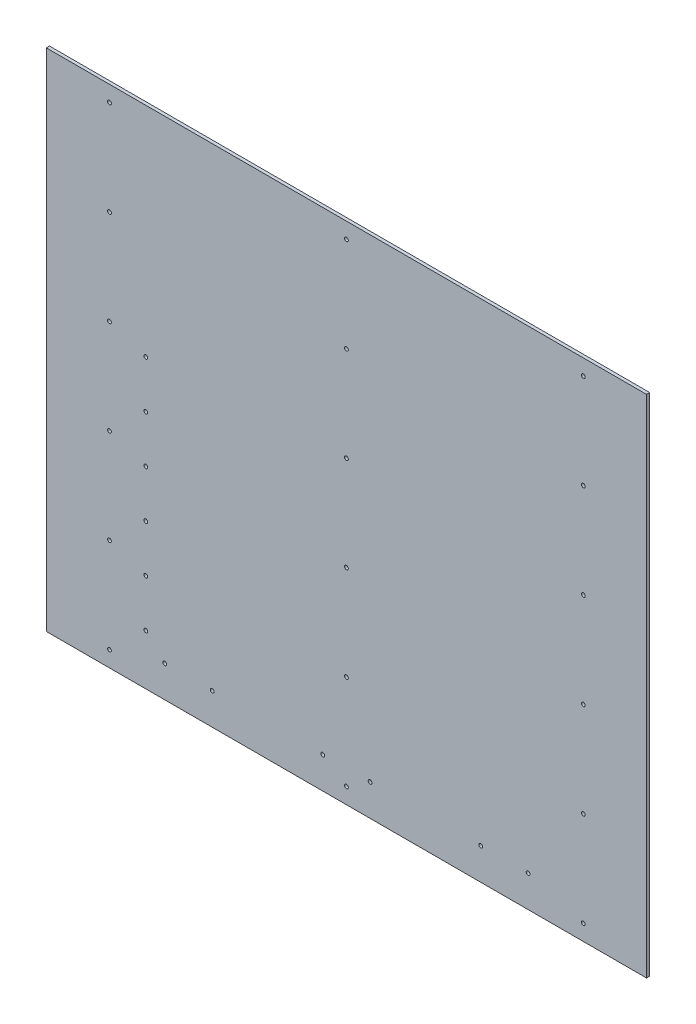
SolidWorks part; units mm, degrees
ref_plane "Płaszczyzna przednia" through (0, 0, 0) normal (0, 0, 1) x (1, 0, 0)
ref_plane "Płaszczyzna górna" through (0, 0, 0) normal (0, 1, 0) x (1, 0, 0)
ref_plane "Płaszczyzna prawa" through (0, 0, 0) normal (1, 0, 0) x (0, 0, -1)
sketch "Szkic1" plane through (0, 0, 0) normal (0, 0, 1) x (1, 0, 0)
  line L1 (-950, -800) -> (950, -800)
  line L2 (-950, -800) -> (-950, 800)
  line L3 (-950, 800) -> (950, 800)
  line L4 (950, -800) -> (950, 800)
  line L5 (-950, -800) -> (950, 800) construction
  line L6 (-950, 800) -> (950, -800) construction
  point P0 (0, 0)
  dimension "D1" = 1900
  dimension "D2" = 1600
extrude "Dodanie-wyciągnięcie1" add sketch "Szkic1" along normal blind 10
hole_wizard "Otwór pod śrubę M101" positions "Szkic2" profile "Szkic3" hole size "M10" standard "Ansi Metric" end condition through all
sketch "Szkic2" plane through (0, 0, 10) normal (0, 0, 1) x (1, 0, 0)
  line L0 (-950, 800) -> (-950, -800) construction
  line L2 (-950, -800) -> (950, -800) construction
  point P0 (-750, -750)
  dimension "D1" = 200
  dimension "D2" = 50
sketch "Szkic3" plane through (-750, -750, 10) normal (1, 0, 0) x (0, -1, 0)
  line L0 (0, 0) -> (0, 10)
  line L1 (0, 10) -> (6, 10)
  line L2 (6, 10) -> (6, 0)
  line L5 (6, 0) -> (0, 0)
  line L11 (0, -6.35) -> (0, 107.95) construction
  dimension "Średnica otworu na wylot" = 12
  dimension "Głębokość otworu na wylot" = 10
pattern_linear "Szyk liniowy1" count 6 spacing 300 along (0, 1, 0) count 3 spacing 750 along (1, 0, 0) of "Otwór pod śrubę M101"
hole_wizard "Otwór pod śrubę M103" positions "Szkic6" profile "Szkic7" hole size "M10" standard "Ansi Metric" end condition through all
sketch "Szkic6" plane through (0, 0, 10) normal (0, 0, 1) x (1, 0, 0)
  line L0 (-950, -800) -> (950, -800) construction
  circle A0 centre (0, -750) radius 6 construction
  point P0 (-75, -700)
  point P2 (75, -700)
  dimension "D1" = 100
  dimension "D2" = 100
  dimension "D3" = 150
  dimension "D4" = 75
sketch "Szkic7" plane through (-75, -700, 10) normal (1, 0, 0) x (0, -1, 0)
  line L0 (0, 0) -> (0, 10)
  line L1 (0, 10) -> (6, 10)
  line L2 (6, 10) -> (6, 0)
  line L5 (6, 0) -> (0, 0)
  line L11 (0, -6.35) -> (0, 107.95) construction
  dimension "Średnica otworu na wylot" = 12
  dimension "Głębokość otworu na wylot" = 10
hole_wizard "Otwór pod śrubę M104" positions "Szkic8" profile "Szkic9" hole size "M10" standard "Ansi Metric" end condition through all
sketch "Szkic8" plane through (0, 0, 10) normal (0, 0, 1) x (1, 0, 0)
  line L0 (-950, -800) -> (950, -800) construction
  circle A0 centre (0, -750) radius 6 construction
  point P0 (-575, -700)
  point P2 (-425, -700)
  point P4 (425, -700)
  point P6 (575, -700)
  dimension "D7" = 575
  dimension "D8" = 575
  dimension "D1" = 100
  dimension "D2" = 100
  dimension "D3" = 100
  dimension "D4" = 100
  dimension "D5" = 150
  dimension "D6" = 150
sketch "Szkic9" plane through (-575, -700, 10) normal (1, 0, 0) x (0, -1, 0)
  line L0 (0, 0) -> (0, 10)
  line L1 (0, 10) -> (6, 10)
  line L2 (6, 10) -> (6, 0)
  line L5 (6, 0) -> (0, 0)
  line L11 (0, -6.35) -> (0, 107.95) construction
  dimension "Średnica otworu na wylot" = 12
  dimension "Głębokość otworu na wylot" = 10
hole_wizard "Otwór pod śrubę M105" positions "Szkic10" profile "Szkic11" hole size "M10" standard "Ansi Metric" end condition through all
sketch "Szkic10" plane through (0, 0, 10) normal (0, 0, 1) x (1, 0, 0)
  point P0 (-635, 110)
  point P3 (-635, -40)
  point P6 (-635, -190)
  point P9 (-635, -340)
  point P12 (-635, -490)
  point P15 (-635, -640)
sketch "Szkic11" plane through (-635, 110, 10) normal (1, 0, 0) x (0, -1, 0)
  line L0 (0, 0) -> (0, 10)
  line L1 (0, 10) -> (6, 10)
  line L2 (6, 10) -> (6, 0)
  line L5 (6, 0) -> (0, 0)
  line L11 (0, -6.35) -> (0, 107.95) construction
  dimension "Średnica otworu na wylot" = 12
  dimension "Głębokość otworu na wylot" = 10
